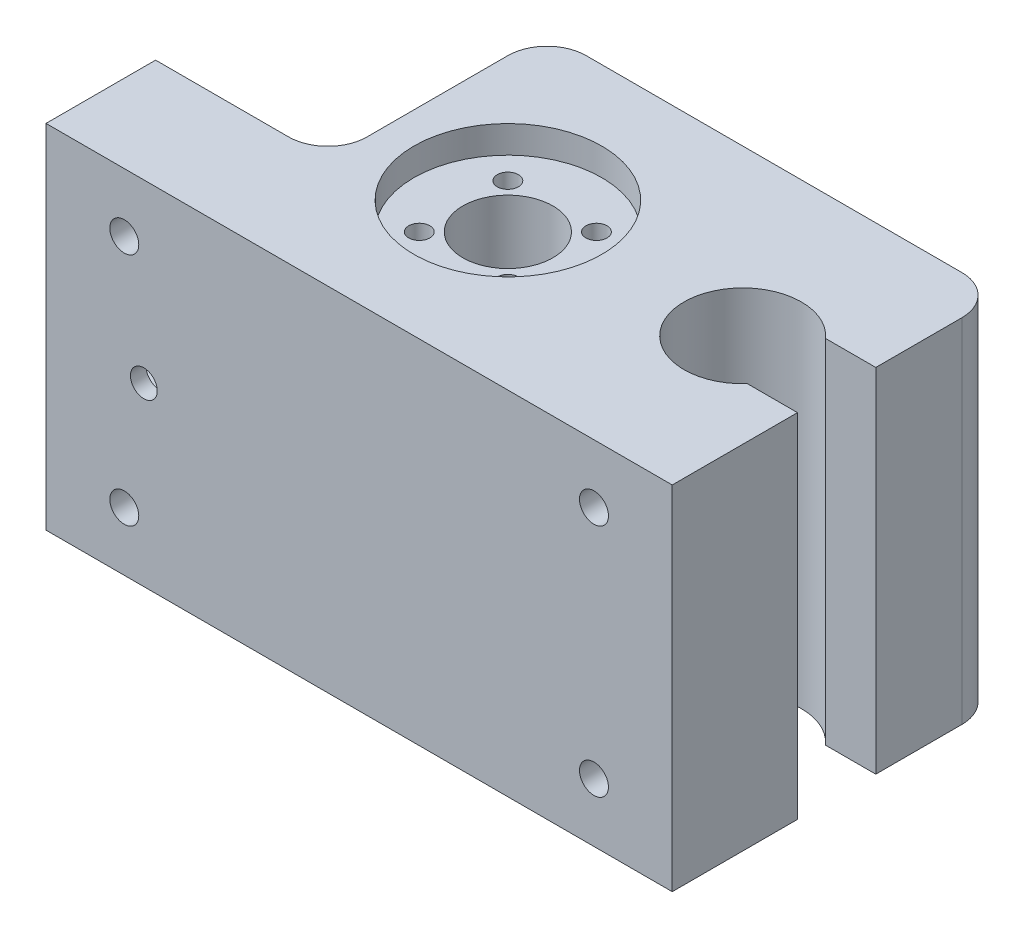
SolidWorks part; units mm, degrees
ref_plane "Front Plane" through (0, 0, 0) normal (0, 0, 1) x (1, 0, 0)
ref_plane "Top Plane" through (0, 0, 0) normal (0, 1, 0) x (1, 0, 0)
ref_plane "Right Plane" through (0, 0, 0) normal (1, 0, 0) x (0, 0, -1)
sketch "Sketch1" plane through (0, 0, 0) normal (0, 0, 1) x (1, 0, 0)
  line L0 (80, 22.5) -> (0, 22.5) construction
  line L1 (0, 0) -> (80, 0)
  line L2 (0, 0) -> (0, 45)
  line L3 (0, 45) -> (80, 45)
  line L4 (80, 0) -> (80, 45)
  dimension "D1" = 80
  dimension "D2" = 45
extrude "Boss-Extrude1" add sketch "Sketch1" along normal blind 42
sketch "Sketch3" plane through (0, 45, 0) normal (0, 1, 0) x (1, 0, 0)
  line L0 (0, -28) -> (22, -28)
  line L1 (0, -42) -> (0, 0) construction
  line L2 (22, -28) -> (22, 0)
  line L3 (80, 0) -> (0, 0) construction
  line L4 (22, 0) -> (0, 0)
  line L5 (0, 0) -> (0, -28)
  dimension "D1" = 28
  dimension "D2" = 22
extrude "Cut-Extrude2" cut sketch "Sketch3" against normal through all
sketch "Sketch4" plane through (0, 0, 0) normal (-1, 0, 0) x (0, 0, 1)
  line L0 (42, 45) -> (42, 0) construction
  line L1 (30, 31) -> (40, 31)
  line L2 (30, 31) -> (30, 14)
  line L3 (30, 14) -> (40, 14)
  line L4 (40, 31) -> (40, 14)
  line L5 (28, 0) -> (28, 45) construction
  line L6 (42, 45) -> (28, 45) construction
  dimension "D1" = 17
  dimension "D2" = 2
  dimension "D3" = 2
  dimension "D4" = 14
extrude "Cut-Extrude3" cut sketch "Sketch4" against normal blind 28
sketch "Sketch7" plane through (0, 45, 0) normal (0, 1, 0) x (1, 0, 0)
  circle A0 centre (38, -21) radius 12
  dimension "D1" = 24
extrude "Cut-Extrude5" cut sketch "Sketch7" against normal blind 3.5 contours A0
sketch "Sketch11" plane through (0, 41.5, 0) normal (0, 1, 0) x (1, 0, 0)
  circle A0 centre (43.6569, -15.3431) radius 1.35
  circle A1 centre (43.6569, -26.6569) radius 1.35
  circle A2 centre (32.3431, -26.6569) radius 1.35
  circle A3 centre (32.3431, -15.3431) radius 1.35
  dimension "D1" = 2.7
extrude "Cut-Extrude6" cut sketch "Sketch11" against normal blind 15
sketch "Sketch12" plane through (0, 41.5, 0) normal (0, 1, 0) x (1, 0, 0)
  circle A0 centre (38, -21) radius 5.75
  dimension "D1" = 11.5
extrude "Cut-Extrude7" cut sketch "Sketch12" against normal through all contours A0
sketch "Sketch13" plane through (0, 45, 0) normal (0, 1, 0) x (1, 0, 0)
  circle A0 centre (68, -21) radius 7.5
  dimension "D1" = 15
extrude "Cut-Extrude8" cut sketch "Sketch13" against normal through all
sketch "Sketch14" plane through (0, 45, 0) normal (0, 1, 0) x (1, 0, 0)
  line L0 (68, -21) -> (80, -21) construction
  line L1 (80, -42) -> (80, 0) construction
  line L3 (67.9005, -26) -> (80, -26)
  line L4 (67.9005, -26) -> (67.9005, -16)
  line L5 (67.9005, -16) -> (80, -16)
  line L6 (80, -26) -> (80, -16)
  line L7 (67.9005, -26) -> (80, -16) construction
  line L8 (67.9005, -16) -> (80, -26) construction
  point P5 (73.9502, -21)
  dimension "D1" = 10
extrude "Cut-Extrude9" cut sketch "Sketch14" against normal through all
sketch "Sketch15" plane through (0, 0, 42) normal (0, 0, 1) x (1, 0, 0)
  circle A0 centre (12.5, 22.5) radius 1.7123
extrude "Cut-Extrude10" cut sketch "Sketch15" against normal through all
sketch "Sketch16" plane through (0, 0, 42) normal (0, 0, 1) x (1, 0, 0)
  line L0 (80, 22.5) -> (0, 22.5) construction
  line L1 (80, 0) -> (80, 45) construction
  line L2 (0, 45) -> (0, 0) construction
  line L4 (70, 7.5) -> (10, 7.5) construction
  line L5 (70, 7.5) -> (70, 37.5) construction
  line L6 (70, 37.5) -> (10, 37.5) construction
  line L7 (10, 7.5) -> (10, 37.5) construction
  line L8 (70, 7.5) -> (10, 37.5) construction
  line L9 (70, 37.5) -> (10, 7.5) construction
  circle A0 centre (10, 37.5) radius 1.85
  circle A1 centre (70, 37.5) radius 1.85
  circle A2 centre (70, 7.5) radius 1.85
  circle A3 centre (10, 7.5) radius 1.85
  point P6 (40, 22.5)
  dimension "D3" = 3.7
  dimension "D4" = 3.7
  dimension "D5" = 3.7
  dimension "D6" = 3.7
  dimension "D1" = 30
  dimension "D2" = 60
extrude "Cut-Extrude11" cut sketch "Sketch16" against normal blind 8
fillet "Fillet2" radius 5 3 edges at (22, 22.5, 28) (22, 22.5, 0) (80, 22.5, 0)
sketch "Sketch17" plane through (0, 0, 0) normal (0, -1, 0) x (1, 0, 0)
  circle A0 centre (38, 21) radius 12.5
  dimension "D1" = 25
extrude "Cut-Extrude12" cut sketch "Sketch17" against normal blind 31
